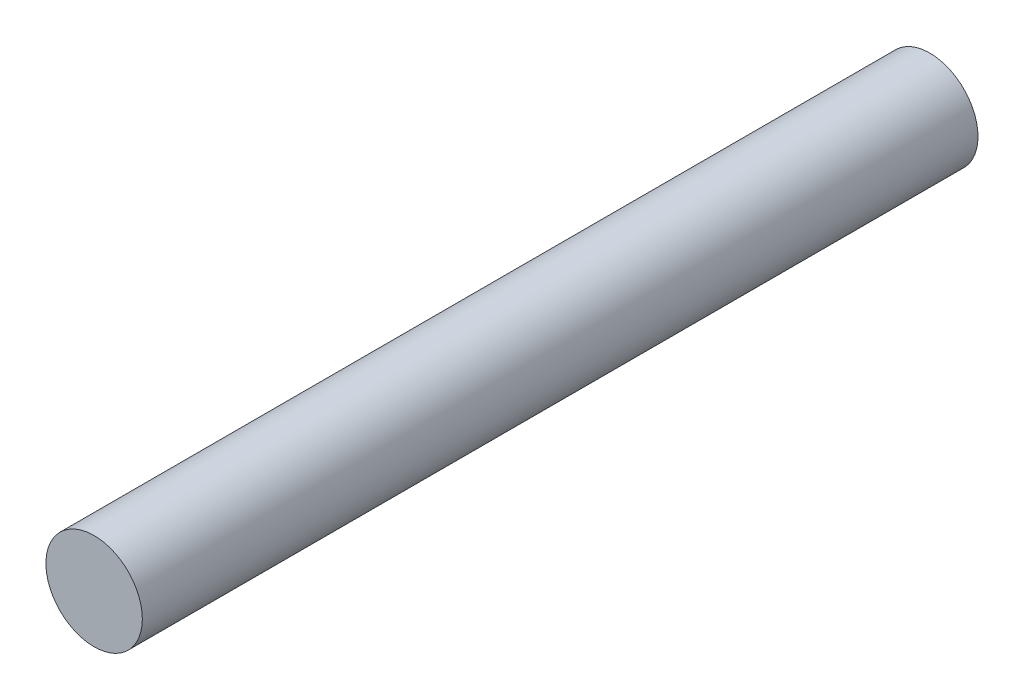
SolidWorks part; units mm, degrees
ref_plane "Front Plane" through (0, 0, 0) normal (0, 0, 1) x (1, 0, 0)
ref_plane "Top Plane" through (0, 0, 0) normal (0, 1, 0) x (1, 0, 0)
ref_plane "Right Plane" through (0, 0, 0) normal (1, 0, 0) x (0, 0, -1)
sketch "Sketch1" plane through (0, 0, 0) normal (0, 0, 1) x (1, 0, 0)
  circle A0 centre (0, 0) radius 75
  dimension "D1" = 150
extrude "Boss-Extrude1" add sketch "Sketch1" along normal blind 1300
sketch "Sketch2" plane through (0, 0, 0) normal (0, 0, -1) x (-1, 0, 0)
  circle A0 centre (0, 0) radius 32.7891
extrude "Cut-Extrude1" cut sketch "Sketch2" against normal blind 209
